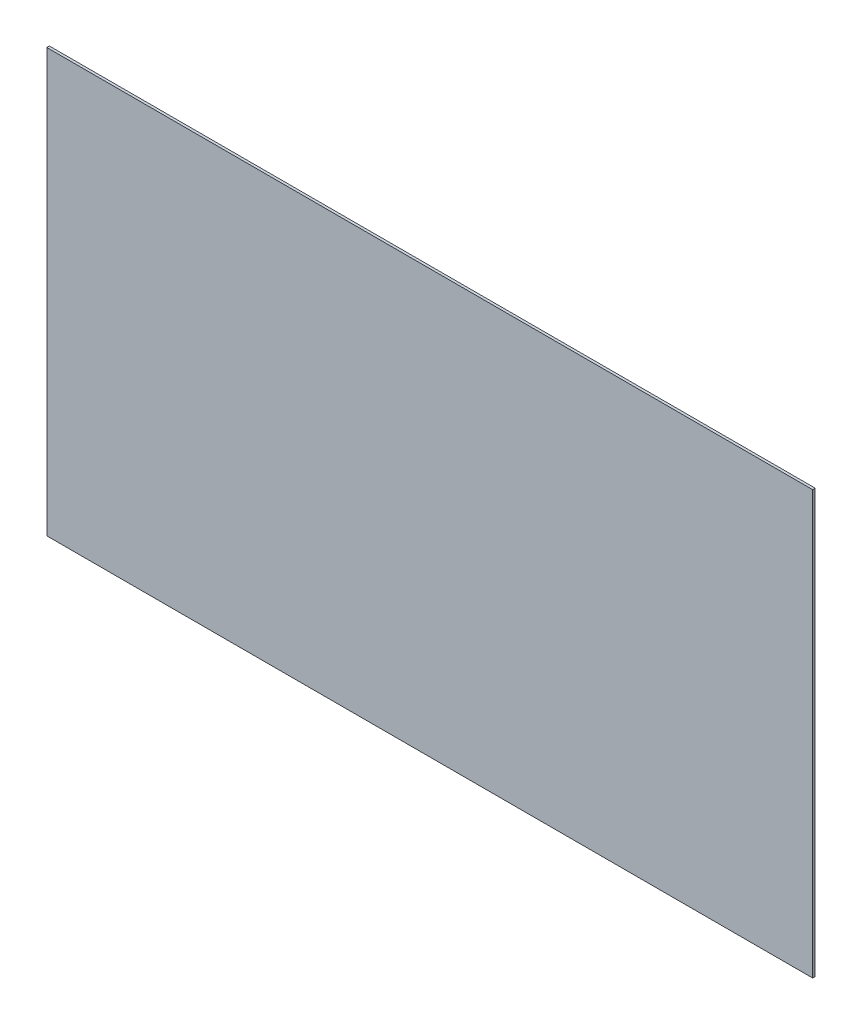
SolidWorks part; units mm, degrees
ref_plane "Front Plane" through (0, 0, 0) normal (0, 0, 1) x (1, 0, 0)
ref_plane "Top Plane" through (0, 0, 0) normal (0, 1, 0) x (1, 0, 0)
ref_plane "Right Plane" through (0, 0, 0) normal (1, 0, 0) x (0, 0, -1)
sketch "Sketch2" plane through (0, 0, 0) normal (0, 0, 1) x (1, 0, 0)
  line L1 (-300.4, 165.91) -> (300.4, 165.91)
  line L2 (-300.4, 165.91) -> (-300.4, -165.91)
  line L3 (-300.4, -165.91) -> (300.4, -165.91)
  line L4 (300.4, 165.91) -> (300.4, -165.91)
  line L5 (-300.4, 165.91) -> (300.4, -165.91) construction
  line L6 (-300.4, -165.91) -> (300.4, 165.91) construction
  point P0 (0, 0)
  dimension "Length 1" = 600.8
  dimension "Length 2" = 331.82
extrude "Boss-Extrude1" add sketch "Sketch2" along normal blind 2.032
